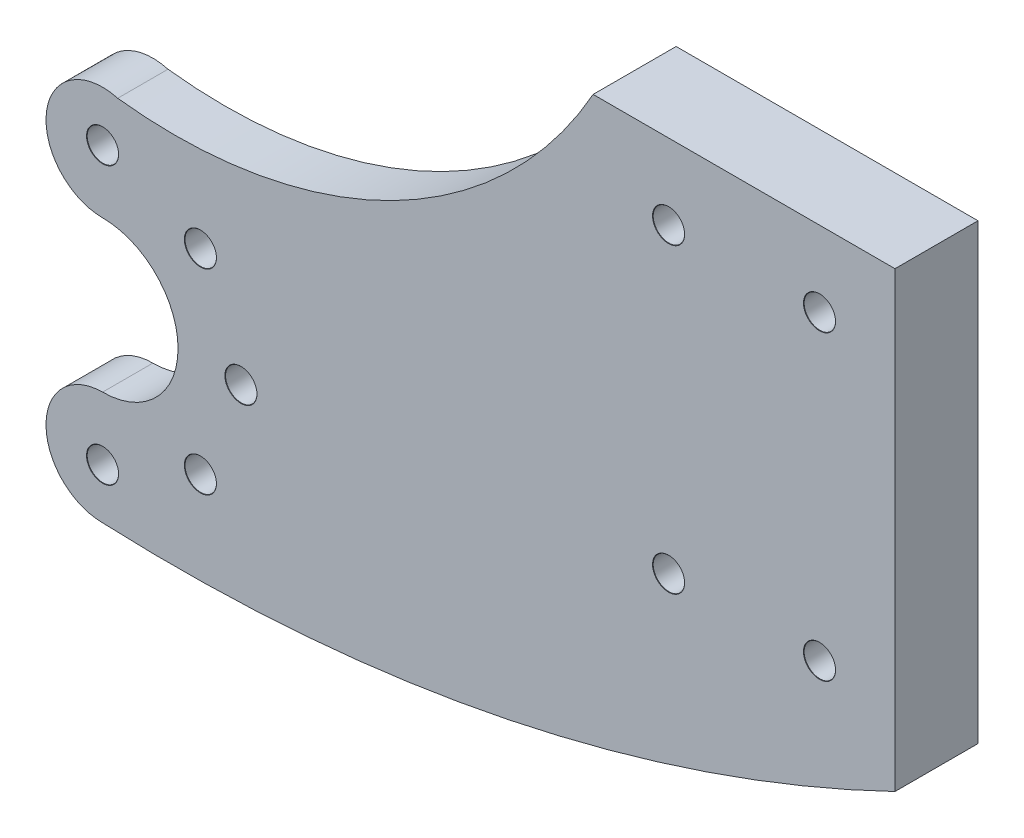
SolidWorks part; units mm, degrees
ref_plane "前视基准面" through (0, 0, 0) normal (0, 0, 1) x (1, 0, 0)
ref_plane "上视基准面" through (0, 0, 0) normal (0, 1, 0) x (1, 0, 0)
ref_plane "右视基准面" through (0, 0, 0) normal (1, 0, 0) x (0, 0, -1)
sketch "草图1" plane through (0, 0, 0) normal (0, 0, 1) x (1, 0, 0)
  line L1 (0, 0) -> (-24, 0)
  line L2 (0, 0) -> (0, 36)
  line L3 (0, 36) -> (-24, 36)
  line L4 (-24, 0) -> (-24, 36)
  dimension "D1" = 36
  dimension "D2" = 24
extrude "凸台-拉伸1" add sketch "草图1" along normal blind 2.6
sketch "草图4" plane through (0, 0, 2.6) normal (0, 0, 1) x (1, 0, 0)
  line L0 (-63, 16.999) -> (-63, -12.999)
  line L1 (-12, 36) -> (-12, 0) construction
  line L2 (-24, 36) -> (0, 36)
  line L3 (0, 36) -> (0, 0)
  line L4 (-63, 2) -> (-77.0817, 2) construction
  line L5 (-24, 18) -> (0, 18) construction
  line L6 (-24, 36) -> (-24, 0) construction
  line L7 (-63, 16.999) -> (-63, 8)
  line L8 (-63, -12.999) -> (-63, -4)
  arc A3 (-63, -12.999) -> (0, 0) centre (-57.2579, 118.3371) ccw
  arc A4 (-63, 16.999) -> (-24, 36) centre (-57.2497, 54.7211) ccw
  circle A5 centre (-63, 2) radius 6
  circle A6 centre (-63, 12.5) radius 4.499
  circle A7 centre (-63, -8.5) radius 4.499
  line M7 (0, 0) -> (0, 36)
  line M8 (0, 36) -> (-24, 36)
  line M9 (-24, 36) -> (-24, 0)
  line M10 (-24, 0) -> (0, 0)
  dimension "D4" = 16
  dimension "D6" = 12
  dimension "D3" = 51
extrude "凸台-拉伸2" add sketch "草图4" along normal blind 4 contours A5 L0 A3 A4 M10 M9 | M10 M7 M8 M9 | A6 | A7 region at (-38.1122, 4.6974, 2.6) region at (-12, 18, 2.6)
hole_wizard "Ø2.5mm 暗销孔1" positions "草图5" profile "草图6" hole size "Ø2.5" standard "ISO" end condition through all
sketch "草图5" plane through (0, 0, 6.6) normal (0, 0, 1) x (1, 0, 0)
  line L0 (-63, 2) -> (-63, 12.3527) construction
  circle A1 centre (-63, 2) radius 1.4731 construction
  point P14 (-63, 13)
  point P21 (-55.2218, 9.7782)
  point P22 (-52, 2)
  point P23 (-55.2218, -5.7782)
  point P24 (-63, -9)
  dimension "D1" = 11
  dimension "D2" = 5
sketch "草图6" plane through (-63, -9, 6.6) normal (1, 0, 0) x (0, -1, 0)
  line L0 (0, 0) -> (0, 6.6)
  line L1 (0, 6.6) -> (1.25, 6.6)
  line L2 (1.25, 6.6) -> (1.25, 0.025)
  line L3 (1.25, 0.025) -> (1.275, 0)
  line L5 (1.275, 0) -> (0, 0)
  line L6 (-1.25, 0.025) -> (-1.275, 0) construction
  line L11 (0, -6.35) -> (0, 107.95) construction
  dimension "通孔孔直径" = 2.5
  dimension "通孔孔深度" = 6.6
  dimension "近端锥形沉头孔直径" = 2.55
  dimension "近端锥形沉头孔角度" = 90
hole_wizard "Ø2.5mm 暗销孔2" positions "草图7" profile "草图8" hole size "Ø2.5" standard "ISO" end condition through all
sketch "草图7" plane through (0, 0, 6.6) normal (0, 0, 1) x (1, 0, 0)
  line L0 (-12, 36) -> (-12, -8.6488) construction
  line L3 (0, 18) -> (-41.4541, 18) construction
  point P17 (-18, 30)
  point P19 (-18, 6)
  point P21 (-6, 6)
  point P22 (-6, 30)
  dimension "D1" = 24
  dimension "D2" = 12
  dimension "D3" = 6
  dimension "D4" = 6
sketch "草图8" plane through (-6, 30, 6.6) normal (1, 0, 0) x (0, -1, 0)
  line L0 (0, 0) -> (0, 6.6)
  line L1 (0, 6.6) -> (1.25, 6.6)
  line L2 (1.25, 6.6) -> (1.25, 0.025)
  line L3 (1.25, 0.025) -> (1.275, 0)
  line L5 (1.275, 0) -> (0, 0)
  line L6 (-1.25, 0.025) -> (-1.275, 0) construction
  line L11 (0, -6.35) -> (0, 107.95) construction
  dimension "通孔孔直径" = 2.5
  dimension "通孔孔深度" = 6.6
  dimension "近端锥形沉头孔直径" = 2.55
  dimension "近端锥形沉头孔角度" = 90
